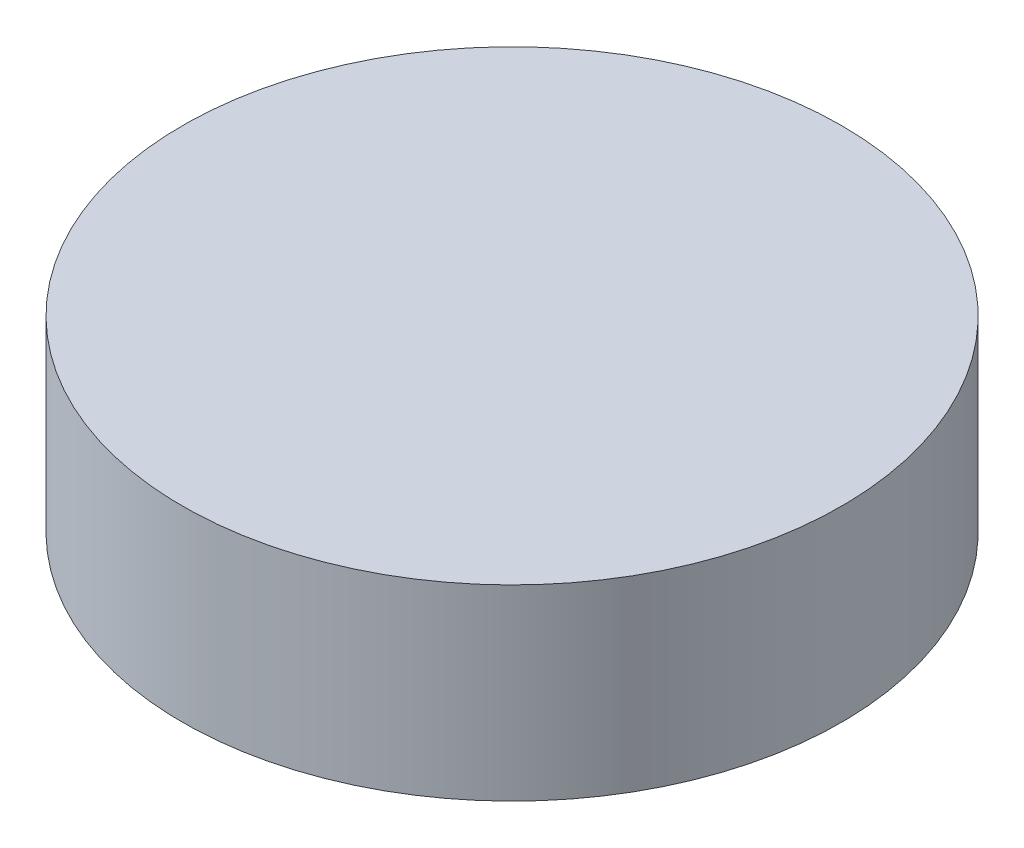
SolidWorks part; units mm, degrees
ref_plane "Front Plane" through (0, 0, 0) normal (0, 0, 1) x (1, 0, 0)
ref_plane "Top Plane" through (0, 0, 0) normal (0, 1, 0) x (1, 0, 0)
ref_plane "Right Plane" through (0, 0, 0) normal (1, 0, 0) x (0, 0, -1)
sketch "Sketch1" plane through (0, 0, 0) normal (0, 1, 0) x (1, 0, 0)
  circle A0 centre (0, 0) radius 268.217
extrude "Boss-Extrude1" add sketch "Sketch1" along normal blind 152.4
sketch "Sketch2" plane through (0, 0, 67.6953) normal (0, 0, 1) x (1, 0, 0)
  line L1 (-14.733, 88.729) -> (93.183, 88.729)
  line L2 (-14.733, 88.729) -> (-14.733, 16.4857)
  line L3 (-14.733, 16.4857) -> (93.183, 16.4857)
  line L4 (93.183, 88.729) -> (93.183, 16.4857)
extrude "Cut-Extrude3" cut sketch "Sketch2" against normal up to surface (135.3905 mm away) rebuild error yes
